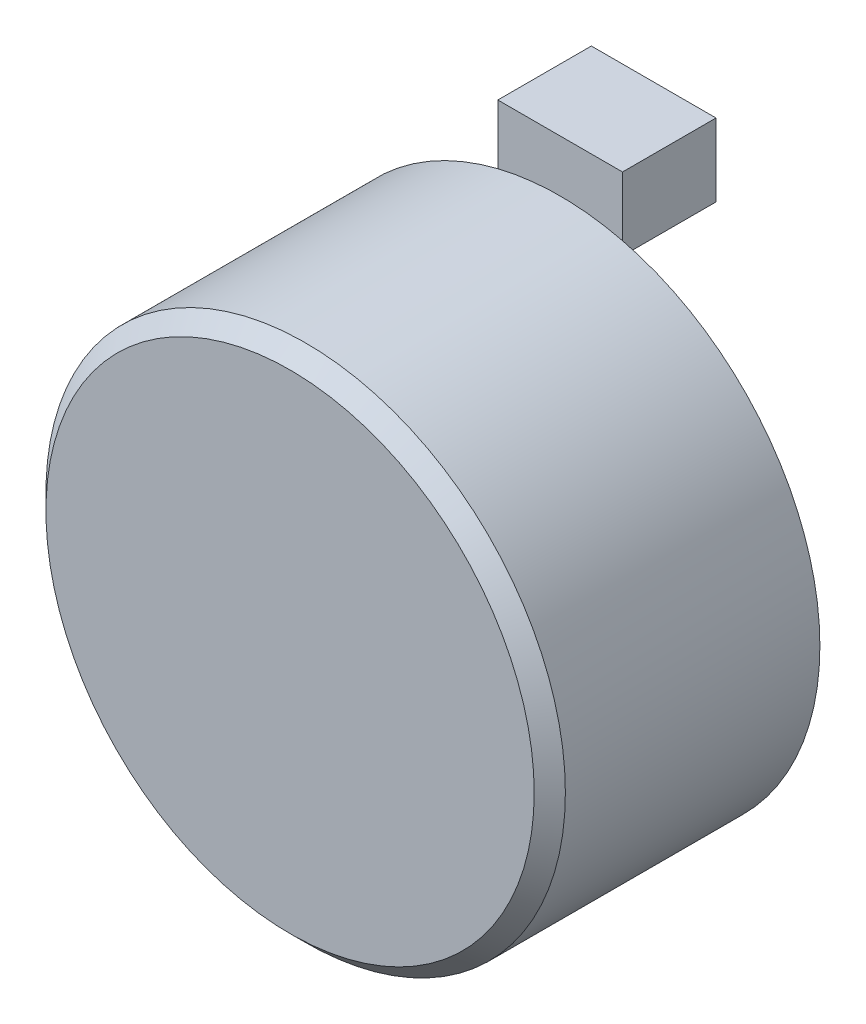
SolidWorks part; units mm, degrees
ref_plane "Front Plane" through (0, 0, 0) normal (0, 0, 1) x (1, 0, 0)
ref_plane "Top Plane" through (0, 0, 0) normal (0, 1, 0) x (1, 0, 0)
ref_plane "Right Plane" through (0, 0, 0) normal (1, 0, 0) x (0, 0, -1)
sketch "SK_Body" plane through (0, 0, 0) normal (0, 1, 0) x (1, 0, 0)
  line L0 (0, -10) -> (0, 62) construction
  line L1 (0, 0) -> (47, 0)
  line L2 (47, 0) -> (50, 3)
  line L3 (50, 3) -> (50, 52)
  line L4 (50, 52) -> (47, 52)
  line L5 (47, 52) -> (0, 52)
  line L6 (0, 52) -> (0, 0)
  dimension "P1" = 10
  dimension "P2" = 62
  dimension "R_front" = 47
  dimension "P4" = 50
  dimension "P5" = 3
  dimension "R_body" = 50
  dimension "L_body" = 52
  dimension "P8" = 47
  dimension "P9" = 52
  dimension "P10" = 52
revolve "Housing_Body" add sketch "SK_Body" angle 360 about L0
ref_plane "PL_Rear" through (0, 0, -52) normal (0, 0, 1) x (1, 0, 0)
sketch "SK_RearHole" plane through (0, 0, -52) normal (0, 0, 1) x (1, 0, 0)
  circle A0 centre (42, 0) radius 1.65
  dimension "D_rh" = 3.3
  dimension "R_rh" = 42
extrude "Rear_Tapped_Hole" cut sketch "SK_RearHole" along normal blind 8
ref_axis "AX_Joint" through (0, 0, -73.5) along (0, 0, 1)
pattern_circular "Rear_Hole_Pattern" count 8 over 360 about axis through (0, 0, -73.5) along (0, 0, 1) of "Rear_Tapped_Hole"
sketch "SK_Connector" plane through (0, 0, -52) normal (0, 0, 1) x (1, 0, 0)
  line L0 (-12, 46) -> (12, 46)
  line L1 (12, 46) -> (12, 60)
  line L2 (12, 60) -> (-12, 60)
  line L3 (-12, 60) -> (-12, 46)
  dimension "P1" = 12
  dimension "P2" = 46
  dimension "P3" = 12
  dimension "P4" = 46
  dimension "P5" = 12
  dimension "P6" = 60
  dimension "P7" = 12
  dimension "P8" = 60
extrude "Connector_Zone" add sketch "SK_Connector" against normal blind 18
equation "\"D_act\" = 100"
equation "\"L_housing\" = 52"
equation "\"PCD_rear\" = 84"
equation "\"D_rear_hole\" = 3.3"
equation "\"D_bearing_boss\" = 60"
equation "\"R_front@SK_Body\" = \"D_act\"/2-3.0"
equation "\"R_body@SK_Body\" = \"D_act\"/2"
equation "\"L_body@SK_Body\" = \"L_housing\""
equation "\"D_rh@SK_RearHole\" = \"D_rear_hole\""
equation "\"R_rh@SK_RearHole\" = \"PCD_rear\"/2"
